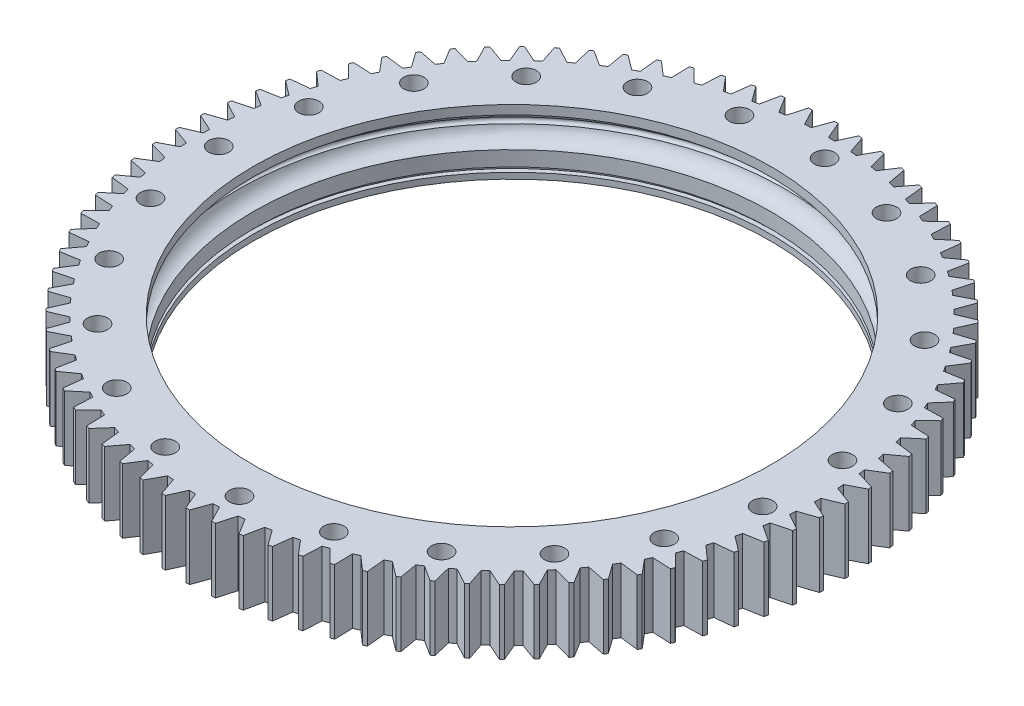
SolidWorks part; units mm, degrees
ref_plane "Plan de face" through (0, 0, 0) normal (0, 0, 1) x (1, 0, 0)
ref_plane "Plan de dessus" through (0, 0, 0) normal (0, 1, 0) x (1, 0, 0)
ref_plane "Plan de droite" through (0, 0, 0) normal (1, 0, 0) x (0, 0, -1)
sketch "Esquisse1" plane through (0, 0, 0) normal (0, 0, 1) x (1, 0, 0)
  line L0 (0, 0) -> (-219.15, 0) construction
  line L1 (-219.15, 0) -> (-219.15, 43) construction
  line L2 (-219.15, 43) -> (0, 43) construction
  line L3 (0, 43) -> (0, 0) construction
  line L4 (-219.15, 0) -> (-172, 0) construction
  line L5 (-172, 0) -> (-172, 10) construction
  line L6 (-172, 10) -> (-172, 30) construction
  line L7 (-172, 43) -> (-172, 42.7532) construction
  line L8 (-172, 43) -> (-219.15, 43) construction
  line L9 (-172, 20) -> (-181.5, 20) construction
  line L10 (-181.5, 20) -> (-183.5, 20) construction
  line L11 (-170, 43) -> (-170, 39) construction
  line L12 (-170, 39) -> (-167, 39) construction
  line L13 (-167, 39) -> (-167, 36) construction
  line L14 (-172, 43) -> (-172, 30) construction
  line L15 (-172, 42.7532) -> (-172, 43) construction
  line L16 (-171, 43) -> (-171, 0) construction
  line L17 (-170, 30) -> (-170, 43) construction
  line L18 (-170, 43) -> (-132.5, 43) construction
  line L19 (-132.5, 43) -> (-132.5, 0) construction
  line L20 (-132.5, 0) -> (-170, 0) construction
  line L21 (-167, 36) -> (-170, 36) construction
  line L22 (-170, 36) -> (-170, 30) construction
  line L23 (-170, 0) -> (-170, 10) construction
  line L24 (-170, 36) -> (-172, 36) construction
  line L25 (-172, 36) -> (-219.15, 36) construction
  line L26 (-219.15, 36) -> (-219.15, -7) construction
  line L27 (-172, 43) -> (-170, 43) construction
  line L28 (-219.15, -7) -> (-172, -7)
  line L29 (-172, 0) -> (-175, 0)
  line L30 (-172, 0) -> (-172, -3) construction
  line L31 (-172, -3) -> (-175, -3)
  line L32 (-175, -3) -> (-175, 0)
  line L33 (-175, 0) -> (-172, 0) construction
  line L34 (-172, 0) -> (-172, -7)
  line L35 (-172, -3) -> (-172, 10)
  line L36 (-172, 36) -> (-172, 30)
  line L37 (-172, 36) -> (-219.15, 36)
  line L38 (-219.15, 36) -> (-219.15, -7)
  arc A0 (-172, 30) -> (-172, 10) centre (-172, 20) ccw
  arc A1 (-181.8026, 21.977) -> (-181.8026, 18.023) centre (-181.5, 20) ccw
  arc A2 (-181.8026, 18.023) -> (-172, 10) centre (-172, 20) ccw construction
  arc A3 (-172, 30) -> (-181.8026, 21.977) centre (-172, 20) ccw construction
  arc A4 (-160.1974, 21.977) -> (-160.1974, 18.023) centre (-160.5, 20) cw construction
  arc A5 (-170, 30) -> (-170, 10) centre (-170, 20) cw construction
  arc A6 (-170, 30) -> (-160.1974, 21.977) centre (-170, 20) cw construction
  arc A7 (-160.1974, 18.023) -> (-170, 10) centre (-170, 20) cw construction
  dimension "D7" = 10
  dimension "D8" = 9.5
  dimension "D9" = 2
  dimension "D2" = 3
  dimension "D3" = 20
  dimension "D4" = 3
  dimension "D5" = 170
  dimension "D6" = 43
  dimension "D10" = 7
  dimension "D11" = 1
  dimension "D12" = 3
  dimension "D13" = 3
  dimension "D14" = 43
  dimension "D15" = 132.5
  dimension "D17" = 219.15
revolve "Révolution1" add sketch "Esquisse1" angle 360 about L3 region at (-197.3492, 14.0988, 0)
sketch "Esquisse4" plane through (0, 36, 0) normal (0, 1, 0) x (1, 0, 0)
  line L0 (0, 0) -> (-195, 0) construction
  circle A0 centre (-195, 0) radius 6.75
  point P38 (0, 0)
  dimension "D1" = 13.5
  dimension "D2" = 195
extrude "Enlèv. mat.-Extru.2" cut sketch "Esquisse4" against normal through all
ref_axis "Axe2" through (0, 45.15, 0) along (0, -1, 0)
pattern_circular "Répétition circulaire1" count 23 over 360 about axis through (0, 45.15, 0) along (0, -1, 0) of "Enlèv. mat.-Extru.2"
sketch "Esquisse5" plane through (0, 36, 0) normal (0, 1, 0) x (1, 0, 0)
  line L0 (0, 0) -> (-219.15, 0) construction
  line L1 (-219.15, 0) -> (-230.5954, 0)
  line L2 (-230.5954, 0) -> (-230.5954, -19.6399)
  line L3 (0, 0) -> (-207.15, -17.643) construction
  line L4 (-207.15, -17.643) -> (-230.5954, -19.6399) construction
  line L5 (-219.15, 0) -> (-219.1006, -4.6547)
  line L6 (-219.1006, -4.6547) -> (-209.8462, -8.0358)
  line L7 (-209.8462, -8.0358) -> (-207.713, -8.8151)
  line L8 (-207.713, -8.8151) -> (-207.4948, -12.9737)
  line L9 (-207.4948, -12.9737) -> (-209.531, -14.0277)
  line L10 (-209.531, -14.0277) -> (-218.3594, -18.5977)
  line L11 (-207.713, -8.8151) -> (-207.9098, -4.1798) construction
  line L12 (-207.9098, -4.1798) -> (-219.1006, -4.6547) construction
  line L13 (-218.3594, -18.5977) -> (-230.5954, -19.6399)
  line L14 (0, 0) -> (-207.4948, -12.9737) construction
  line L15 (0, 0) -> (-207.713, -8.8151) construction
  line L16 (0, 0) -> (-219.1006, -4.6547) construction
  circle A0 centre (0, 0) radius 219.15 construction
  circle A1 centre (0, 0) radius 210
  circle A2 centre (0, 0) radius 207.9
  circle M24 centre (0, 0) radius 219.15
  dimension "D1" = 438.3
  dimension "D2" = 420
  dimension "D7" = 11.25
  dimension "D3" = 1.217
  dimension "D4" = 4.868
  dimension "D5" = 22.5
  dimension "D6" = 22.5
extrude "Enlèv. mat.-Extru.3" cut sketch "Esquisse5" against normal through all contours A2 L7 A1 L9 | A1 L6 L10 M24 | L13 L1 L2 M24 region at (-224.7893, 36, 9.6749) region at (-214.8601, 36, 11.3713) region at (-208.7199, 36, 10.9678)
pattern_circular "Répétition circulaire2" count 84 over 360 about axis through (0, 45.15, 0) along (0, -1, 0) of "Enlèv. mat.-Extru.3"
